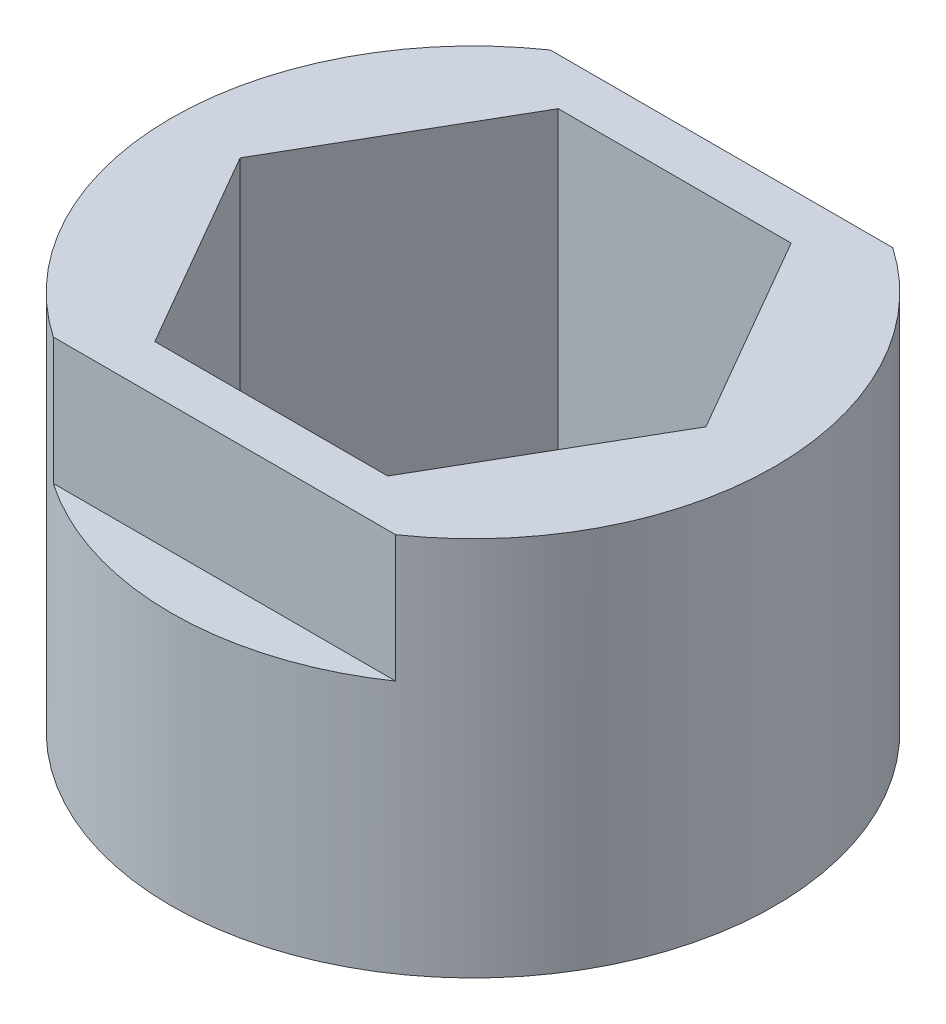
SolidWorks part; units mm, degrees
material "Polyester Resin"
ref_plane "Front Plane" through (0, 0, 0) normal (0, 0, 1) x (1, 0, 0)
ref_plane "Top Plane" through (0, 0, 0) normal (0, 1, 0) x (1, 0, 0)
ref_plane "Right Plane" through (0, 0, 0) normal (1, 0, 0) x (0, 0, -1)
sketch "Sketch1" plane through (0, 0, 0) normal (0, 1, 0) x (1, 0, 0)
  line L1 (-2.9156, 5.05) -> (-5.8312, 0)
  line L2 (-5.8312, 0) -> (-2.9156, -5.05)
  line L3 (-2.9156, -5.05) -> (2.9156, -5.05)
  line L4 (2.9156, -5.05) -> (5.8312, 0)
  line L5 (5.8312, 0) -> (2.9156, 5.05)
  line L6 (2.9156, 5.05) -> (-2.9156, 5.05)
  circle A0 centre (0, 0) radius 5.05 construction
  circle A1 centre (0, 0) radius 7.5565
  dimension "D2" = 15.113
  dimension "D1" = 10.1
extrude "Boss-Extrude1" add sketch "Sketch1" along normal blind 8.89
sketch "Sketch2" plane through (0, 0, 0) normal (0, -1, 0) x (1, 0, 0)
  circle A0 centre (0, 0) radius 7.5565
  circle A1 centre (0, 0) radius 3.3
  dimension "D1" = 6.6
extrude "Boss-Extrude2" add sketch "Sketch2" along normal blind 0.635
sketch "Sketch3" plane through (0, 0, 0) normal (1, 0, 0) x (0, 0, -1)
  line L0 (-6.223, 9.525) -> (-6.223, 5.715)
  line L1 (6.223, 9.525) -> (6.223, 5.715)
  line L2 (-7.5565, -0.635) -> (7.5565, -0.635) construction
  line L3 (-6.223, 9.525) -> (-8.202, 9.525)
  line L4 (-8.202, 9.525) -> (-8.202, 5.715)
  line L5 (-8.202, 5.715) -> (-6.223, 5.715)
  line L6 (6.223, 9.525) -> (8.4791, 9.525)
  line L7 (8.4791, 9.525) -> (8.4791, 5.715)
  line L8 (8.4791, 5.715) -> (6.223, 5.715)
  dimension "D1" = 12.446
  dimension "D2" = 6.223
  dimension "D3" = 3.81
  dimension "D4" = 3.81
  dimension "D5" = 6.35
  dimension "D6" = 6.35
extrude "Cut-Extrude1" cut sketch "Sketch3" against normal through all and the other way through all
equation "\"AB_Central_Bushing_Length\" = .4724in"
equation "\"Solid_Length\"= .025in"
equation "\"Hex_Length\"= 0.35"
equation "\"D1@Boss-Extrude1\"= \"Hex_Length\""
equation "\"D1@Boss-Extrude2\"=\"Solid_Length\""
equation "\"Cutout_Angle\" = 80"
